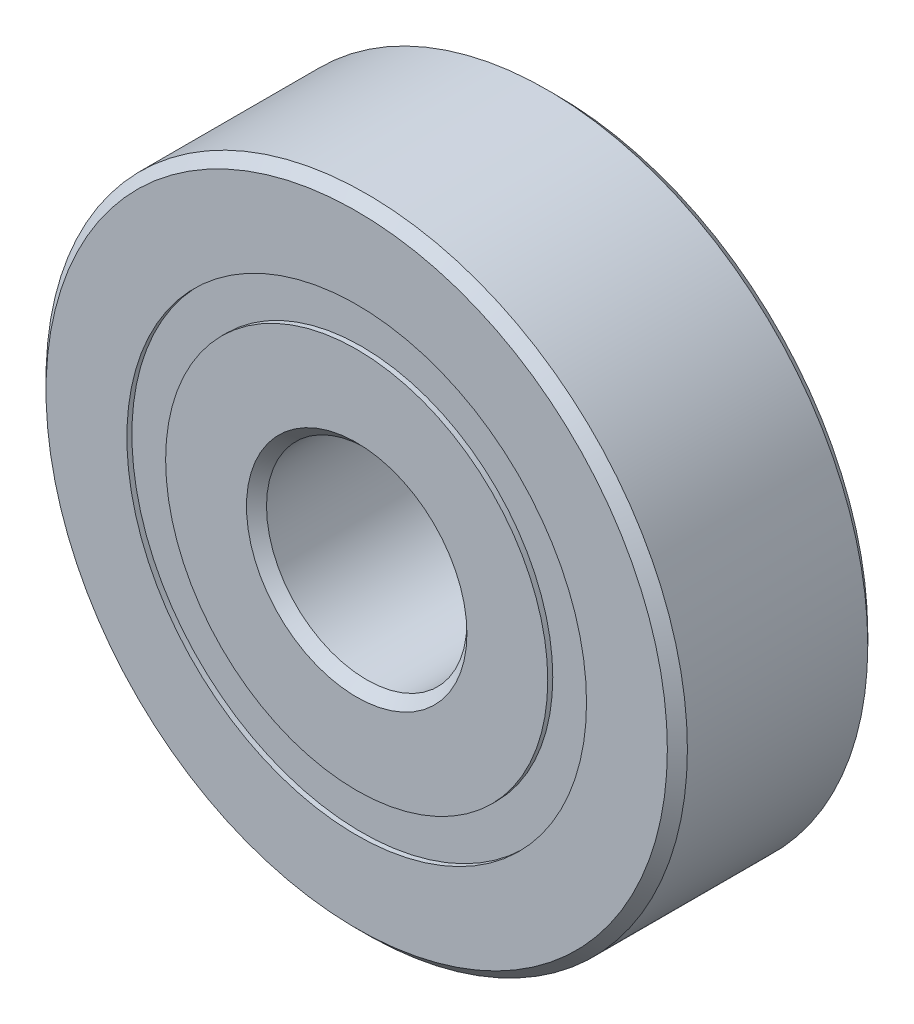
SolidWorks part; units mm, degrees
ref_plane "Front Plane" through (0, 0, 0) normal (0, 0, 1) x (1, 0, 0)
ref_plane "Top Plane" through (0, 0, 0) normal (0, 1, 0) x (1, 0, 0)
ref_plane "Right Plane" through (0, 0, 0) normal (1, 0, 0) x (0, 0, -1)
sketch "Sketch1" plane through (0, 0, 0) normal (1, 0, 0) x (0, 0, -1)
  line L0 (-2.5, 0) -> (2.5, 0) construction
  line L1 (0, 8) -> (0, -8) construction
  line L2 (2.25, 8) -> (-2.25, 8)
  line L3 (-2.25, 8) -> (-2.5, 7.75)
  line L4 (-2.5, 7.75) -> (-2.5, 5.7335)
  line L5 (-2.5, 5.7335) -> (-1.1111, 5.7335)
  line L6 (2.5, 5.7335) -> (1.1111, 5.7335)
  line L7 (2.5, 7.75) -> (2.5, 5.7335)
  line L8 (2.25, 8) -> (2.5, 7.75)
  line L9 (0, 8) -> (0, 5.25) construction
  line L10 (0, 5.25) -> (0, 2.5) construction
  arc A0 (-1.1111, 5.7335) -> (1.1111, 5.7335) centre (0, 5.25) cw
  point P14 (0, 2.5)
  dimension "D3" = 2.2222
  dimension "D1" = 45
  dimension "Width" = 5
  dimension "OD" = 16
  dimension "D2" = 0.25
  dimension "Shaft Dia" = 5
  dimension "D4" = 0.4835
revolve "Revolve1" add sketch "Sketch1" angle 360 about L0
sketch "Sketch3" plane through (0, 0, 0) normal (1, 0, 0) x (0, 0, -1)
  line L0 (-2.5, 4.7665) -> (-1.1111, 4.7665)
  line L1 (0, 8) -> (0, -8) construction
  line L2 (-2.5, 7.75) -> (-2.5, 5.7335) construction
  line L3 (-2.5, 4.7665) -> (-2.5, 2.75)
  line L4 (-2.25, 8) -> (-2.5, 7.75) construction
  line L5 (-2.5, 2.75) -> (-2.25, 2.5)
  line L6 (-2.25, 2.5) -> (2.25, 2.5)
  line L7 (2.25, 8) -> (2.25, -8) construction
  line L8 (2.25, 2.5) -> (2.5, 2.75)
  line L9 (2.5, -7.75) -> (2.5, 7.75) construction
  line L10 (2.5, 2.75) -> (2.5, 4.7665)
  line L11 (2.5, 4.7665) -> (1.1111, 4.7665)
  line L13 (2.25, 8) -> (2.5, 7.75) construction
  arc A0 (1.1111, 5.7335) -> (-1.1111, 5.7335) centre (0, 5.25) ccw construction
  arc A1 (1.1111, 4.7665) -> (-1.1111, 4.7665) centre (0, 5.25) cw
revolve "Revolve3" add sketch "Sketch3" angle 360 about L0
sketch "Sketch4" plane through (0, 0, 0) normal (1, 0, 0) x (0, 0, -1)
  line L0 (-1.2118, 5.25) -> (1.2118, 5.25)
  arc A2 (-1.2118, 5.25) -> (1.2118, 5.25) centre (0, 5.25) cw
  arc A3 (1.1111, 5.7335) -> (-1.1111, 5.7335) centre (0, 5.25) ccw construction
revolve "Revolve4" add sketch "Sketch4" angle 360 about L0
ref_axis "Axis1" through (0, 0, -2.5) along (0, 0, 1)
pattern_circular "CirPattern1" count 10 every 36 about axis through (0, 0, -2.5) along (0, 0, 1) of bodies 104
sketch "Sketch5" plane through (0, 0, 0) normal (1, 0, 0) x (0, 0, -1)
  line L0 (-2.5, 5.7335) -> (-1.1111, 5.7335) construction
  line L1 (-2.375, 5.7335) -> (-1.2118, 5.7335)
  line L2 (-2.375, 5.7335) -> (-2.375, 4.7665)
  line L3 (-2.375, 4.7665) -> (-1.2118, 4.7665)
  line L4 (-1.2118, 5.7335) -> (-1.2118, 4.7665)
  line L5 (-2.5, 4.7665) -> (-1.1111, 4.7665) construction
  line L6 (2.5, 5.7335) -> (1.1111, 5.7335) construction
  line L7 (2.375, 5.7335) -> (1.2118, 5.7335)
  line L8 (2.375, 5.7335) -> (2.375, 4.7665)
  line L9 (2.375, 4.7665) -> (1.2118, 4.7665)
  line L10 (1.2118, 5.7335) -> (1.2118, 4.7665)
  line L11 (2.5, 4.7665) -> (1.1111, 4.7665) construction
  line L12 (-2.25, 8) -> (-2.5, 7.75) construction
  point P18 (-2.375, 7.875)
revolve "Revolve5" add sketch "Sketch5" angle 360 about L0
equation "\"D2@Sketch1\" = \"Width@Sketch1\"*.05"
equation "\"D3@Sketch1\" = \"Width@Sketch1\"/2.25"
equation "\"D4@Sketch1\" = (((\"OD@Sketch1\"-\"Width@Sketch1\")/2)/3.25)/3.5"
equation "\"D2@CirPattern1\" = 360/\"Balls@CirPattern1\""
